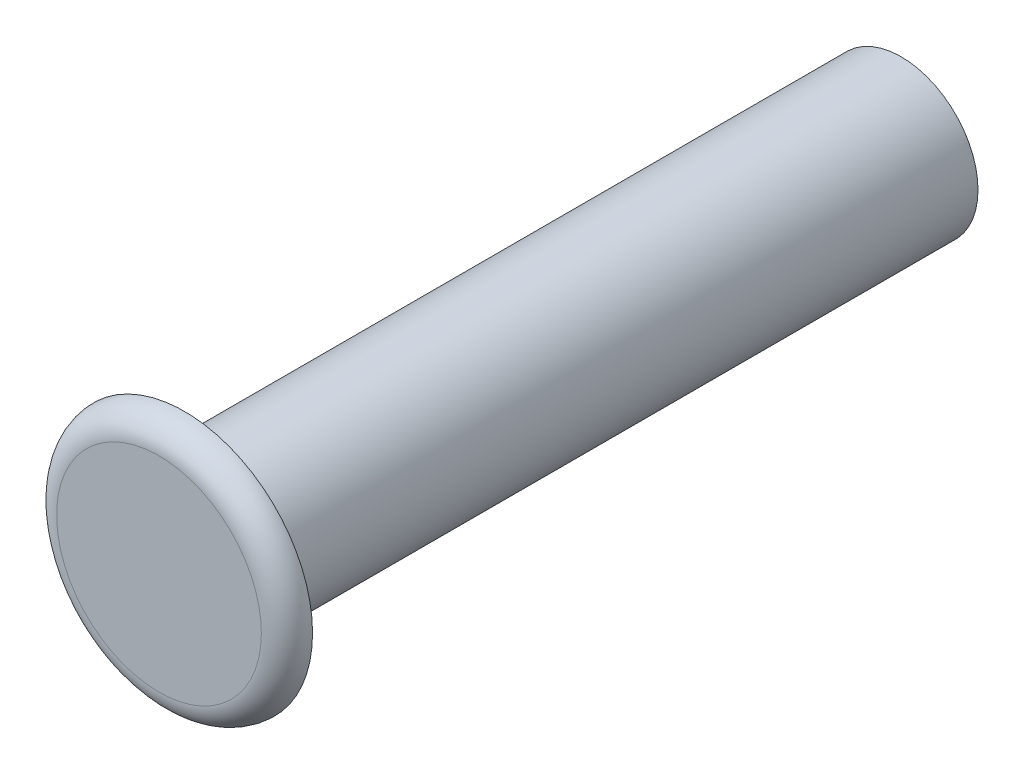
SolidWorks part; units mm, degrees
ref_plane "前视基准面" through (0, 0, 0) normal (0, 0, 1) x (1, 0, 0)
ref_plane "上视基准面" through (0, 0, 0) normal (0, 1, 0) x (1, 0, 0)
ref_plane "右视基准面" through (0, 0, 0) normal (1, 0, 0) x (0, 0, -1)
sketch "草图1" plane through (0, 0, 0) normal (0, 0, 1) x (1, 0, 0)
  circle A0 centre (0, 0) radius 1.5
  dimension "D1" = 3
extrude "凸台-拉伸1" add sketch "草图1" along normal blind 14
sketch "草图2" plane through (0, 0, 14) normal (0, 0, 1) x (1, 0, 0)
  circle A0 centre (0, 0) radius 2.5
  dimension "D1" = 5
extrude "凸台-拉伸2" add sketch "草图2" along normal blind 0.5
fillet "圆角1" radius 0.5 1 edges at (2.5, 0, 14.5)
